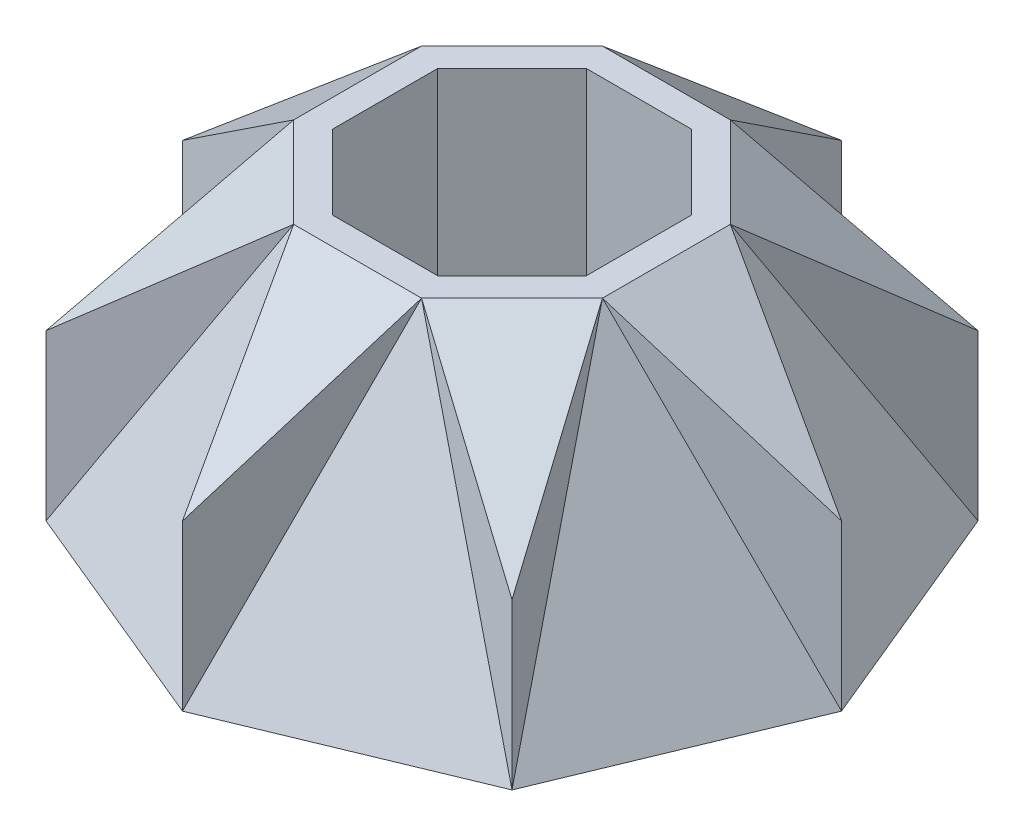
SolidWorks part; units mm, degrees
ref_plane "前视基准面" through (0, 0, 0) normal (0, 0, 1) x (1, 0, 0)
ref_plane "上视基准面" through (0, 0, 0) normal (0, 1, 0) x (1, 0, 0)
ref_plane "右视基准面" through (0, 0, 0) normal (1, 0, 0) x (0, 0, -1)
other "Configuration Table"
sketch "草图1" plane through (0, 0, 0) normal (0, 1, 0) x (1, 0, 0)
  line L1 (42.4264, -42.4264) -> (60, 0)
  line L2 (60, 0) -> (42.4264, 42.4264)
  line L3 (42.4264, 42.4264) -> (0, 60)
  line L4 (0, 60) -> (-42.4264, 42.4264)
  line L5 (-42.4264, 42.4264) -> (-60, 0)
  line L6 (-60, 0) -> (-42.4264, -42.4264)
  line L7 (-42.4264, -42.4264) -> (0, -60)
  line L8 (0, -60) -> (42.4264, -42.4264)
  line L9 (23.112, -9.5733) -> (23.112, 9.5733)
  line L10 (23.112, 9.5733) -> (9.5733, 23.112)
  line L11 (9.5733, 23.112) -> (-9.5733, 23.112)
  line L12 (-9.5733, 23.112) -> (-23.112, 9.5733)
  line L13 (-23.112, 9.5733) -> (-23.112, -9.5733)
  line L14 (-23.112, -9.5733) -> (-9.5733, -23.112)
  line L15 (-9.5733, -23.112) -> (9.5733, -23.112)
  line L16 (9.5733, -23.112) -> (23.112, -9.5733)
  circle A0 centre (0, 0) radius 60 construction
  circle A1 centre (0, 0) radius 25.0162 construction
extrude "凸台-拉伸1" add sketch "草图1" along normal blind 55
sketch "草图2" plane through (0, 55, 0) normal (0, 1, 0) x (1, 0, 0)
  line L8 (0, -60) -> (42.4264, -42.4264)
  line L9 (42.4264, -42.4264) -> (60, 0)
  line L10 (60, 0) -> (42.4264, 42.4264)
  line L11 (42.4264, 42.4264) -> (0, 60)
  line L12 (0, 60) -> (-42.4264, 42.4264)
  line L13 (-42.4264, 42.4264) -> (-60, 0)
  line L14 (-60, 0) -> (-42.4264, -42.4264)
  line L15 (-42.4264, -42.4264) -> (0, -60)
  line L16 (0, -60) -> (42.4264, -42.4264)
  line L17 (42.4264, -42.4264) -> (60, 0)
  line L18 (60, 0) -> (42.4264, 42.4264)
  line L19 (42.4264, 42.4264) -> (0, 60)
  line L20 (0, 60) -> (-42.4264, 42.4264)
  line L21 (-42.4264, 42.4264) -> (-60, 0)
  line L22 (-60, 0) -> (-42.4264, -42.4264)
  line L23 (-42.4264, -42.4264) -> (0, -60)
  line L70 (-28.112, 11.6444) -> (-28.112, -11.6444)
  line L71 (-28.112, -11.6444) -> (-11.6444, -28.112)
  line L72 (-11.6444, -28.112) -> (11.6444, -28.112)
  line L73 (11.6444, -28.112) -> (28.112, -11.6444)
  line L74 (28.112, -11.6444) -> (28.112, 11.6444)
  line L75 (28.112, 11.6444) -> (11.6444, 28.112)
  line L76 (11.6444, 28.112) -> (-11.6444, 28.112)
  line L77 (-11.6444, 28.112) -> (-28.112, 11.6444)
  line L78 (-28.112, 11.6444) -> (-28.112, -11.6444)
  line L79 (-28.112, -11.6444) -> (-11.6444, -28.112)
  line L80 (-11.6444, -28.112) -> (11.6444, -28.112)
  line L81 (11.6444, -28.112) -> (28.112, -11.6444)
  line L82 (28.112, -11.6444) -> (28.112, 11.6444)
  line L83 (28.112, 11.6444) -> (11.6444, 28.112)
  line L84 (11.6444, 28.112) -> (-11.6444, 28.112)
  line L85 (-11.6444, 28.112) -> (-28.112, 11.6444)
  dimension "D1" = 0
  dimension "D2" = 5
ref_plane "基准面2" through (-17.5797, 20.8847, 42.4412) normal (-0.3484, 0.4139, 0.841) x (0.9374, 0.1538, 0.3126)
sketch "草图4" plane through (-17.5797, 20.8847, 42.4412) normal (-0.3484, 0.4139, 0.841) x (0.9374, 0.1538, 0.3126)
  line L0 (6.332, 36.9366) -> (-26.5072, -18.7323)
  line L1 (-26.5072, -18.7323) -> (18.7546, -26.4915)
  line L2 (18.7546, -26.4915) -> (6.332, 36.9366)
extrude "切除-拉伸3" cut sketch "草图4" along direction (0, -1, 0) on the side of the normal through all
sketch "草图5" plane through (0, 55, 0) normal (0, 1, 0) x (1, 0, 0)
  circle A0 centre (0, 0) radius 10.626
sketch "草图6" plane through (0, 0, 0) normal (0, -1, 0) x (1, 0, 0)
  circle A0 centre (0, 0) radius 13.887
ref_axis "基准轴1" through (0, 55, 0) along (0, -1, 0)
pattern_circular "阵列(圆周)1" count 8 over 360 about axis through (0, 55, 0) along (0, -1, 0) of "切除-拉伸3"
sketch "草图7" plane through (0, 0, 0) normal (0, 0, 1) x (1, 0, 0)
  line L0 (-60, 0) -> (-60, 30)
  line L1 (-60, 55) -> (-60, 0) construction
  dimension "D1" = 30
ref_plane "基准面3" through (-37.4067, 47.713, 0) normal (0.617, -0.787, 0) x (-0.787, -0.617, 0)
sketch "草图8" plane through (-37.4067, 47.713, 0) normal (0.617, -0.787, 0) x (-0.787, -0.617, 0)
  line L0 (-11.8107, 11.6444) -> (-11.8107, -11.6444)
  line L1 (-11.8107, -11.6444) -> (28.7098, 0)
  line L2 (28.7098, 0) -> (-11.8107, 11.6444)
extrude "切除-拉伸4" cut sketch "草图8" along direction (0, -1, 0) on the side against the normal through all
pattern_circular "阵列(圆周)2" count 8 over 360 about axis through (0, 55, 0) along (0, -1, 0) of "切除-拉伸4"
